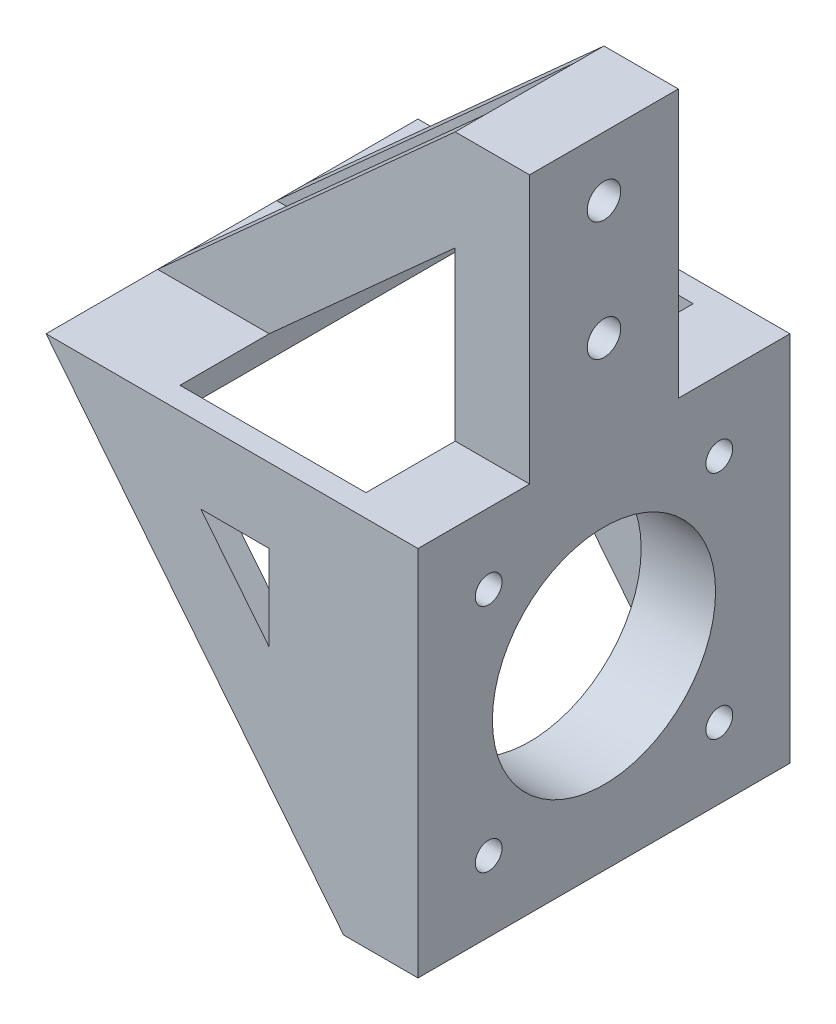
SolidWorks part; units mm, degrees
ref_plane "Front Plane" through (0, 0, 0) normal (0, 0, 1) x (1, 0, 0)
ref_plane "Top Plane" through (0, 0, 0) normal (0, 1, 0) x (1, 0, 0)
ref_plane "Right Plane" through (0, 0, 0) normal (1, 0, 0) x (0, 0, -1)
sketch "Sketch1" plane through (0, 0, 0) normal (0, 1, 0) x (1, 0, 0)
  line L1 (-10, -10) -> (10, -10)
  line L2 (-10, -10) -> (-10, 10)
  line L3 (-10, 10) -> (10, 10)
  line L4 (10, -10) -> (10, 10)
  line L5 (-10, -10) -> (10, 10) construction
  line L6 (-10, 10) -> (10, -10) construction
  line L7 (-14, 14) -> (14, 14)
  line L8 (-14, 14) -> (-14, -14)
  line L9 (-14, -14) -> (14, -14)
  line L10 (14, 14) -> (14, -14)
  line L11 (-14, 14) -> (14, -14) construction
  line L12 (-14, -14) -> (14, 14) construction
  point P0 (0, 0)
  point P5 (0, 0)
  dimension "D1" = 20
  dimension "D2" = 28
extrude "Boss-Extrude1" add sketch "Sketch1" along normal blind 40
sketch "Sketch2" plane through (-14, 0, 0) normal (-1, 0, 0) x (0, 0, 1)
  line L0 (0, 40) -> (0, 32)
  line L1 (0, 0) -> (0, 16)
  line L4 (-14, 0) -> (14, 0)
  line L5 (14, 0) -> (14, 40)
  line L6 (14, 40) -> (-14, 40)
  line L7 (-14, 40) -> (-14, 0)
  line L8 (-14, 0) -> (14, 0)
  line L9 (14, 0) -> (14, 40)
  line L10 (14, 40) -> (-14, 40)
  line L11 (-14, 40) -> (-14, 0)
  circle A0 centre (0, 32) radius 2.25
  circle A1 centre (0, 16) radius 2.25
  dimension "D3" = 4.5
  dimension "D5" = 4.5
  dimension "D2" = 8
  dimension "D4" = 16
  dimension "D1" = 0
extrude "Cut-Extrude1" cut sketch "Sketch2" against normal blind 30 contours A1 | A0 region at (-14, 33.546, 1.546) region at (-14, 17.546, -1.546)
sketch "Sketch5" plane through (-14, 0, 0) normal (-1, 0, 0) x (0, 0, 1)
  line L0 (0, 0) -> (0, -21)
  line L1 (0, -21) -> (-15.4998, -5.5002) construction
  line L2 (-25, -46) -> (25, -46)
  line L3 (-25, -46) -> (-25, 4)
  line L4 (-14, 0) -> (14, 0)
  line L5 (14, 0) -> (14, 40)
  line L6 (14, 40) -> (-14, 40)
  line L7 (-14, 40) -> (-14, 0)
  line L8 (-14, 0) -> (14, 0)
  line L9 (14, 0) -> (14, 40)
  line L10 (14, 40) -> (-14, 40)
  line L11 (-14, 40) -> (-14, 0)
  line L12 (-25, 4) -> (25, 4)
  line L13 (25, -46) -> (25, 4)
  line L14 (-25, -46) -> (25, 4) construction
  line L15 (-25, 4) -> (25, -46) construction
  line L16 (-15.4998, -5.5002) -> (15.4998, -5.5002) construction
  line L17 (15.4998, -5.5002) -> (15.4998, -36.4998) construction
  line L18 (15.4998, -36.4998) -> (-15.4998, -36.4998) construction
  circle A0 centre (-15.4998, -5.5002) radius 1.8
  circle A1 centre (15.4998, -5.5002) radius 1.8
  circle A2 centre (15.4998, -36.4998) radius 1.8
  circle A3 centre (-15.4998, -36.4998) radius 1.8
  circle A4 centre (0, -21) radius 15
  line M7 (-14, 0) -> (14, 0)
  line M8 (14, 0) -> (14, 40)
  dimension "D5" = 3.6
  dimension "D6" = 30
  dimension "D2" = 21
  dimension "D3" = 50
  dimension "D4" = 21.92
  dimension "D1" = 0
extrude "Boss-Extrude2" add sketch "Sketch5" against normal up to surface (4 mm away) contours A4 L11 L12 L3 L2 L13 A3 A2 A1 A0 M7 M8 region at (-14, -0.7071, 7) up to face at (-10, 16, -2.25)
sketch "Sketch6" plane through (0, 0, 0) normal (0, -1, 0) x (1, 0, 0)
  line L0 (-10, 14) -> (14, 14) construction
  line L1 (-10, 14) -> (14, 14)
  line L2 (-10, 14) -> (-10, -14)
  line L3 (-10, -14) -> (14, -14)
  line L4 (14, 14) -> (14, -14)
  dimension "D1" = 24
extrude "Cut-Extrude2" cut sketch "Sketch6" against normal blind 40
sketch "Sketch7" plane through (-14, 0, 0) normal (-1, 0, 0) x (0, 0, 1)
  line L0 (-10, 0) -> (10, 0)
  line L1 (-10, 0) -> (-10, 40)
  line L2 (-14, 40) -> (14, 40) construction
  line L3 (-10, 40) -> (10, 40)
  line L4 (10, 40) -> (10, 0)
  line L6 (-14, 40) -> (-10, 40)
  line L7 (-14, 40) -> (-14, 4)
  line L8 (-14, 4) -> (-10, 4)
  line L9 (-10, 40) -> (-10, 4)
  line L10 (14, 40) -> (10, 40)
  line L11 (14, 40) -> (14, 4)
  line L12 (14, 4) -> (10, 4)
  line L13 (10, 40) -> (10, 4)
  point P4 (0, 0)
  line M7 (-14, 40) -> (-14, 4)
  line M13 (14, 4) -> (14, 40)
  line M14 (14, 40) -> (-14, 40)
  dimension "D1" = 20
  dimension "D2" = 36
  dimension "D3" = 4
  dimension "D4" = 36
  dimension "D5" = 4
extrude "Cut-Extrude3" cut sketch "Sketch7" against normal blind 4 contours L8 L1 M7 M14 | L12 L4 M13 M14 region at (-14, 22, -12) region at (-14, 22, 12)
sketch "Sketch8" plane through (-14, 0, 0) normal (-1, 0, 0) x (0, 0, 1)
  line L8 (10, 40) -> (-10, 40)
  line L9 (-10, 40) -> (-10, 4)
  line L10 (-10, 4) -> (-25, 4)
  line L11 (-25, 4) -> (-25, -46)
  line L12 (-25, -46) -> (25, -46)
  line L13 (25, -46) -> (25, 4)
  line L14 (25, 4) -> (10, 4)
  line L15 (10, 4) -> (10, 40)
  line L16 (10, 40) -> (-10, 40)
  line L17 (-10, 40) -> (-10, 4)
  line L18 (-10, 4) -> (-25, 4)
  line L19 (-25, 4) -> (-25, -46)
  line L20 (-25, -46) -> (25, -46)
  line L21 (25, -46) -> (25, 4)
  line L22 (25, 4) -> (10, 4)
  line L23 (10, 4) -> (10, 40)
  circle A0 centre (15.4998, -5.5002) radius 1.8 construction
  circle A1 centre (15.4998, -36.4998) radius 1.8 construction
  circle A2 centre (-15.4998, -36.4998) radius 1.8 construction
  circle A3 centre (0, -21) radius 15 construction
  circle A4 centre (-15.4998, -5.5002) radius 1.8 construction
  circle A5 centre (0, 16) radius 2.25 construction
  circle A6 centre (0, 32) radius 2.25 construction
  circle A7 centre (15.4998, -5.5002) radius 1.8
  circle A8 centre (15.4998, -36.4998) radius 1.8
  circle A9 centre (-15.4998, -36.4998) radius 1.8
  circle A10 centre (0, -21) radius 15
  circle A11 centre (-15.4998, -5.5002) radius 1.8
  circle A12 centre (0, 16) radius 2.25
  circle A13 centre (0, 32) radius 2.25
  dimension "D1" = 0
extrude "Boss-Extrude3" add sketch "Sketch8" along normal blind 6
sketch "Sketch9" plane through (0, 0, 25) normal (0, 0, 1) x (1, 0, 0)
  line L0 (-20, -46) -> (-20, 4)
  line L1 (-20, 4) -> (-60, 4)
  line L2 (-60, 4) -> (-20, -46)
  line L3 (-39.1938, -6) -> (-30, -17.4922)
  line L4 (-30, -17.4922) -> (-30, -6)
  line L5 (-30, -6) -> (-39.1938, -6)
  dimension "D1" = 40
  dimension "D2" = 10
extrude "Boss-Extrude4" add sketch "Sketch9" against normal blind 3
mirror "Mirror1" about plane through (0, 0, 0) normal (0, 0, 1) of "Boss-Extrude4"
sketch "Sketch10" plane through (0, 0, 22) normal (0, 0, -1) x (-1, 0, 0)
  line L0 (60, 4) -> (45, 4)
  line L1 (10, 4) -> (60, 4) construction
  line L2 (45, 4) -> (45, 1)
  line L3 (45, 1) -> (57.6, 1)
  line L4 (60, 4) -> (20, -46) construction
  line L5 (57.6, 1) -> (60, 4)
  dimension "D1" = 15
  dimension "D2" = 3
extrude "Boss-Extrude5" add sketch "Sketch10" along normal up to surface (44 mm away) up to face at (-33.3333, -12.6667, -22)
sketch "Sketch11" plane through (0, 0, -10) normal (0, 0, -1) x (-1, 0, 0)
  line L0 (20, 40) -> (60, 4)
  line L1 (60, 4) -> (45, 4)
  line L2 (10, 4) -> (60, 4) construction
  line L3 (45, 4) -> (20, 26.5)
  line L4 (20, 40) -> (20, 4) construction
  line L5 (20, 26.5) -> (20, 40)
  dimension "D1" = 15
extrude "Boss-Extrude6" add sketch "Sketch11" against normal blind 4
mirror "Mirror2" about plane through (0, 0, 0) normal (0, 0, 1) of "Boss-Extrude6"
